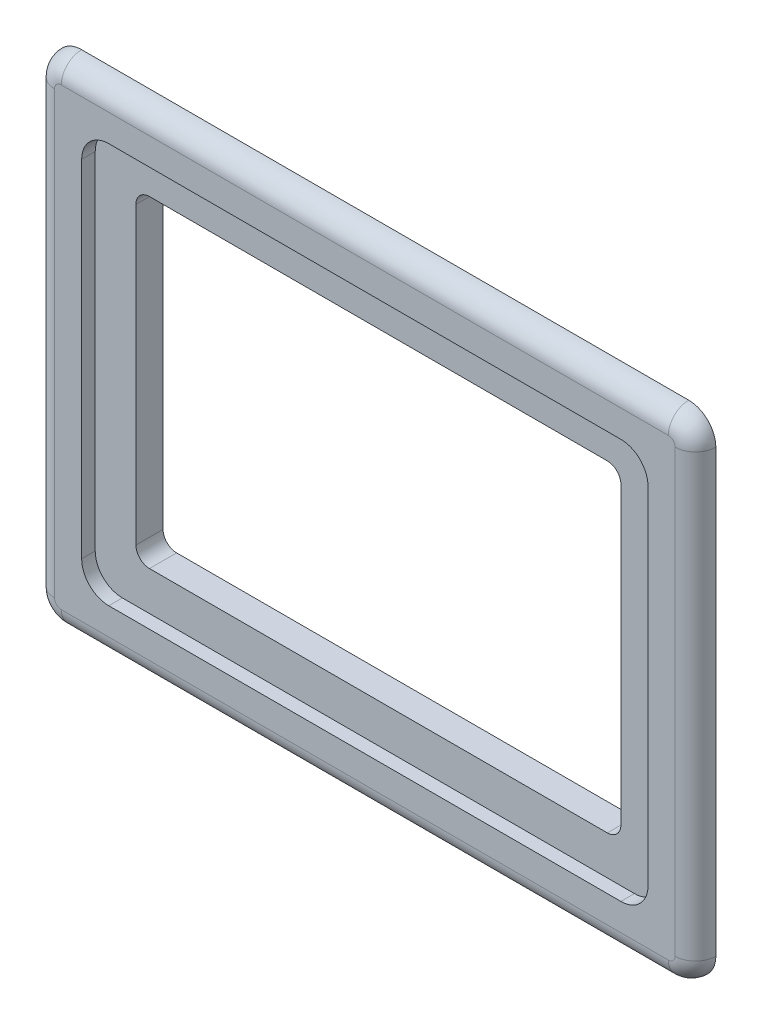
SolidWorks part; units mm, degrees
material "ABS"
ref_plane "Front Plane" through (0, 0, 0) normal (0, 0, 1) x (1, 0, 0)
ref_plane "Top Plane" through (0, 0, 0) normal (0, 1, 0) x (1, 0, 0)
ref_plane "Right Plane" through (0, 0, 0) normal (1, 0, 0) x (0, 0, -1)
sketch "Sketch1" plane through (0, 0, 0) normal (0, 0, 1) x (1, 0, 0)
  line L1 (-154.7812, -115.8875) -> (154.7812, -115.8875)
  line L2 (-154.7812, -115.8875) -> (-154.7812, 115.8875)
  line L3 (-154.7812, 115.8875) -> (154.7812, 115.8875)
  line L4 (154.7812, -115.8875) -> (154.7812, 115.8875)
  line L5 (-154.7812, -115.8875) -> (154.7812, 115.8875) construction
  line L6 (-154.7812, 115.8875) -> (154.7812, -115.8875) construction
  line L11 (-100.7138, -75.4062) -> (100.7138, 75.4063) construction
  line L12 (-100.7138, 75.4063) -> (100.7138, -75.4062) construction
  line L13 (-113.5063, -75.4063) -> (113.5062, -75.4063)
  line L14 (-113.5063, -75.4063) -> (-113.5063, 75.4062)
  line L15 (-113.5063, 75.4062) -> (113.5062, 75.4062)
  line L16 (113.5062, -75.4063) -> (113.5062, 75.4062)
  line L17 (-113.5063, -75.4063) -> (113.5062, 75.4062) construction
  line L18 (-113.5063, 75.4062) -> (113.5062, -75.4063) construction
  line L19 (-132.5562, -93.6625) -> (132.5562, -93.6625)
  line L20 (-132.5562, -93.6625) -> (-132.5562, 93.6625)
  line L21 (-132.5562, 93.6625) -> (132.5562, 93.6625)
  line L22 (132.5562, -93.6625) -> (132.5562, 93.6625)
  line L23 (-132.5562, -93.6625) -> (132.5562, 93.6625) construction
  line L24 (-132.5562, 93.6625) -> (132.5562, -93.6625) construction
  point P0 (0, 0)
  point P6 (0, 0)
  point P11 (0, 0)
  point P16 (0, 0)
  dimension "D1" = 309.5625
  dimension "D2" = 231.775
  dimension "D3" = 227.0125
  dimension "D4" = 150.8125
  dimension "D5" = 265.1125
  dimension "D6" = 187.325
extrude "Boss-Extrude1" add sketch "Sketch1" along normal blind 9.525 contours L1 L4 L3 L2 L22 L19 L20 L21 | L19 L22 L21 L20 L16 L13 L14 L15 region at (-150.9141, 0, 0) region at (-129.3101, 0, 0)
extrude "Boss-Extrude2" add sketch "Sketch1<3>" against normal blind 9.525 contours L19 L22 L21 L20 L16 L13 L14 L15 region at (-129.3101, 0, 0)
sketch "Sketch1<3>" plane through (0, 0, 0) normal (0, 0, 1) x (1, 0, 0) same geometry as "Sketch1"
fillet "Fillet1" radius 12.7 8 edges at (132.5562, -93.6625, -4.7625) (132.5562, 93.6625, -4.7625) (-132.5562, 93.6625, -4.7625) (-132.5562, -93.6625, -4.7625) (154.7812, 115.8875, 4.7625) (154.7812, -115.8875, 4.7625) (-154.7812, 115.8875, 4.7625) (-154.7812, -115.8875, 4.7625)
extrude "Cut-Extrude1" cut sketch "Sketch1<4>" along direction (0, 0, 1) on the side against the normal blind 6.35 from surface contours L19 L22 L21 L20 L16 L13 L14 L15 region at (-129.3101, 0, 0) starting at face at (0, 0, 9.525)
sketch "Sketch1<4>" plane through (0, 0, 0) normal (0, 0, 1) x (1, 0, 0) same geometry as "Sketch1"
fillet "Fillet2" radius 6.35 4 edges at (113.5062, -75.4063, -3.175) (-113.5063, -75.4063, -3.175) (113.5062, 75.4062, -3.175) (-113.5063, 75.4062, -3.175)
fillet "Fillet3" radius 12.7 4 edges at (132.5562, 93.6625, 6.35) (132.5562, -93.6625, 6.35) (-132.5562, -93.6625, 6.35) (-132.5562, 93.6625, 6.35)
fillet "Fillet4" radius 9.525 8 edges at (-151.0615, -112.1678, 9.525) (0, -115.8875, 9.525) (151.0615, -112.1678, 9.525) (154.7812, 0, 9.525) (151.0615, 112.1678, 9.525) (0, 115.8875, 9.525) (-151.0615, 112.1678, 9.525) (-154.7812, 0, 9.525)
